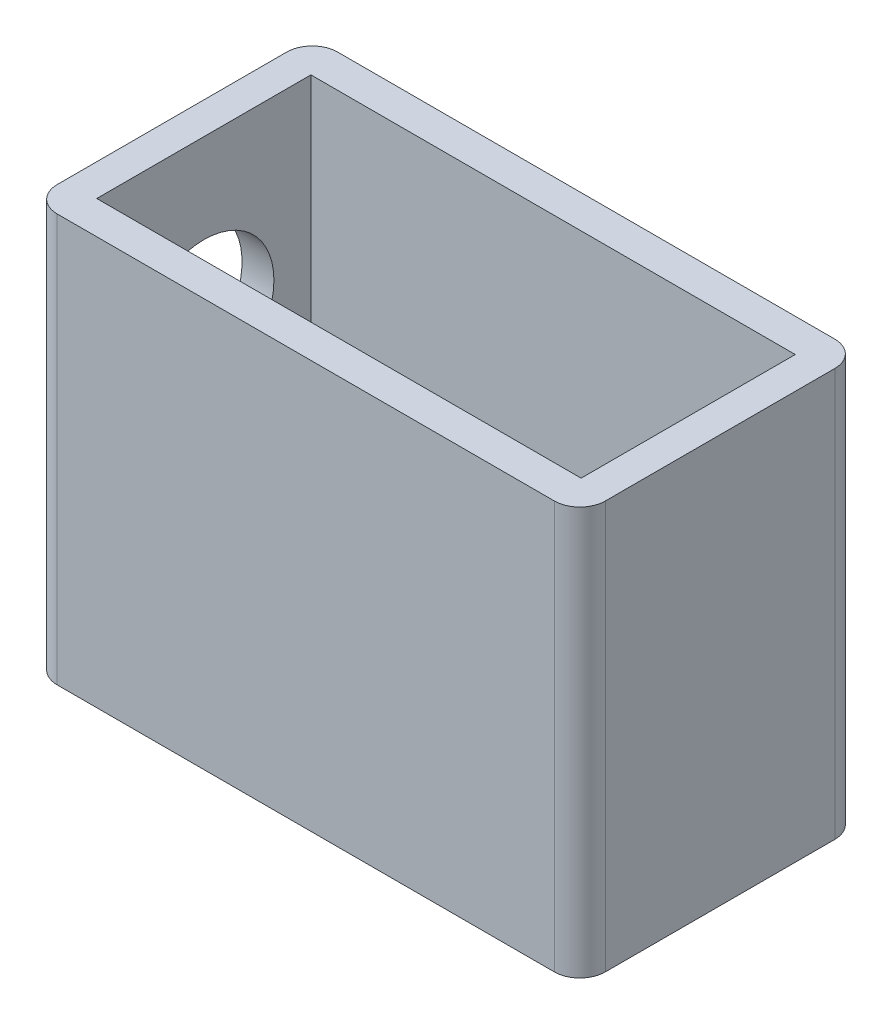
SolidWorks part; units mm, degrees
ref_plane "Front Plane" through (0, 0, 0) normal (0, 0, 1) x (1, 0, 0)
ref_plane "Top Plane" through (0, 0, 0) normal (0, 1, 0) x (1, 0, 0)
ref_plane "Right Plane" through (0, 0, 0) normal (1, 0, 0) x (0, 0, -1)
sketch "Sketch1" plane through (0, 0, 0) normal (0, 1, 0) x (1, 0, 0)
  line L1 (19.5, -11) -> (-19.5, -11)
  line L2 (21.5, -9) -> (21.5, 9)
  line L3 (19.5, 11) -> (-19.5, 11)
  line L4 (-21.5, -9) -> (-21.5, 9)
  line L5 (21.5, -11) -> (-21.5, 11) construction
  line L6 (21.5, 11) -> (-21.5, -11) construction
  arc A0 (19.5, 11) -> (21.5, 9) centre (19.5, 9) cw
  arc A1 (21.5, -9) -> (19.5, -11) centre (19.5, -9) cw
  arc A2 (-19.5, -11) -> (-21.5, -9) centre (-19.5, -9) cw
  arc A3 (-21.5, 9) -> (-19.5, 11) centre (-19.5, 9) cw
  point P0 (0, 0)
  dimension "D3" = 2
  dimension "D1" = 43
  dimension "D2" = 22
extrude "Boss-Extrude1" add sketch "Sketch1" along normal blind 2
sketch "Sketch2" plane through (0, 2, 0) normal (0, 1, 0) x (1, 0, 0)
  line L1 (-17.8, 7.2) -> (1, 7.2)
  line L2 (-17.8, 7.2) -> (-17.8, -8)
  line L3 (-17.8, -8) -> (1, -8)
  line L4 (1, 7.2) -> (1, -8)
  line L5 (2, 7.8) -> (17.8, 7.8)
  line L6 (2, 7.8) -> (2, -8)
  line L7 (2, -8) -> (17.8, -8)
  line L8 (17.8, 7.8) -> (17.8, -8)
  line L10 (-19.5, -11) -> (19.5, -11) construction
  line L14 (-21.5, 9) -> (-21.5, -9) construction
  point P16 (-8.4, -8)
  dimension "D1" = 18.8
  dimension "D2" = 15.2
  dimension "D3" = 15.8
  dimension "D4" = 15.8
  dimension "D5" = 1
  dimension "D6" = 3
  dimension "D7" = 3.7
  dimension "D8" = 3
extrude "Cut-Extrude1" cut sketch "Sketch2" against normal blind 1.4
sketch "Sketch3" plane through (0, 0.6, 0) normal (0, 1, 0) x (1, 0, 0)
  line L0 (1, 7.2) -> (-17.8, 7.2) construction
  line L1 (-16.8, 6.2) -> (0, 6.2)
  line L2 (-16.8, 6.2) -> (-16.8, -7)
  line L3 (-16.8, -7) -> (0, -7)
  line L4 (0, 6.2) -> (0, -7)
  line L5 (3, 6.8) -> (16.8, 6.8)
  line L6 (3, 6.8) -> (3, -7)
  line L7 (3, -7) -> (16.8, -7)
  line L8 (16.8, 6.8) -> (16.8, -7)
  line L9 (-17.8, 7.2) -> (-17.8, -8) construction
  line L10 (-17.8, -8) -> (1, -8) construction
  line L11 (1, -8) -> (1, 7.2) construction
  line L12 (17.8, 7.8) -> (2, 7.8) construction
  line L13 (17.8, -8) -> (17.8, 7.8) construction
  line L14 (2, 7.8) -> (2, -8) construction
  line L15 (2, -8) -> (17.8, -8) construction
  dimension "D1" = 1
  dimension "D2" = 1
  dimension "D3" = 1
  dimension "D4" = 1
  dimension "D5" = 1
  dimension "D6" = 1
  dimension "D7" = 1
  dimension "D8" = 1
extrude "Cut-Extrude2" cut sketch "Sketch3" against normal through all
sketch "Sketch13" plane through (0, 2, 0) normal (0, 1, 0) x (1, 0, 0)
  line L8 (18.5, 8) -> (-18.5, 8)
  line L9 (-18.5, 8) -> (-18.5, -8)
  line L10 (-18.5, -8) -> (18.5, -8)
  line L11 (18.5, -8) -> (18.5, 8)
  line L12 (17.5, 8) -> (-17.5, 8)
  line L13 (-18.5, 7) -> (-18.5, -7)
  line L14 (-17.5, -8) -> (17.5, -8)
  line L15 (18.5, -7) -> (18.5, 7)
  arc A0 (-18.5, 7) -> (-17.5, 8) centre (-17.5, 7) cw
  arc A1 (-17.5, -8) -> (-18.5, -7) centre (-17.5, -7) cw
  arc A2 (17.5, -8) -> (18.5, -7) centre (17.5, -7) ccw
  arc A3 (18.5, 7) -> (17.5, 8) centre (17.5, 7) ccw
  dimension "D2" = 1
  dimension "D1" = 3
extrude "Boss-Extrude3" add sketch "Sketch13" along normal blind 30
fillet "Fillet1" radius 10 1 edges at (17.8, 17, 7.9539)
sketch "Sketch15" plane through (0, 2, 0) normal (0, 1, 0) x (1, 0, 0)
  line L1 (19, -8.4) -> (-19, -8.4)
  line L2 (19, -8.4) -> (19, 8.4)
  line L3 (19, 8.4) -> (-19, 8.4)
  line L4 (-19, -8.4) -> (-19, 8.4)
  line L5 (19, -8.4) -> (-19, 8.4) construction
  line L6 (19, 8.4) -> (-19, -8.4) construction
  point P0 (0, 0)
  dimension "D1" = 16.8
  dimension "D2" = 38
extrude "Cut-Extrude3" cut sketch "Sketch15" along normal through all
sketch "Sketch16" plane through (-21.5, 0, 0) normal (-1, 0, 0) x (0, 0, 1)
  line L0 (-9, 32) -> (9, 32) construction
  circle A0 centre (0, 19.5) radius 5.5
  dimension "D1" = 11
  dimension "D2" = 12.5
extrude "Cut-Extrude4" cut sketch "Sketch16" against normal up to next
